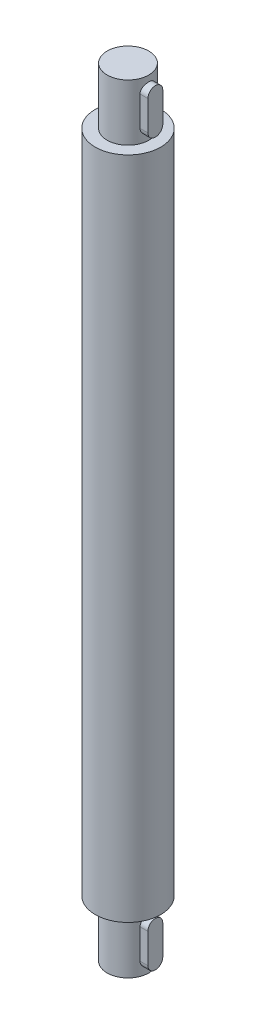
SolidWorks part; units mm, degrees
material "AISI 304"
ref_plane "Front Plane" through (0, 0, 0) normal (0, 0, 1) x (1, 0, 0)
ref_plane "Top Plane" through (0, 0, 0) normal (0, 1, 0) x (1, 0, 0)
ref_plane "Right Plane" through (0, 0, 0) normal (1, 0, 0) x (0, 0, -1)
sketch "Sketch1" plane through (0, 0, 0) normal (0, 1, 0) x (1, 0, 0)
  circle A0 centre (0, 0) radius 7
  dimension "D1" = 14
extrude "Boss-Extrude1" add sketch "Sketch1" along normal blind 19
sketch "Sketch2" plane through (0, 19, 0) normal (0, 1, 0) x (1, 0, 0)
  circle A0 centre (0, 0) radius 11
  dimension "D1" = 22
extrude "Boss-Extrude2" add sketch "Sketch2" along normal blind 223.5
sketch "Sketch3" plane through (0, 242.5, 0) normal (0, 1, 0) x (1, 0, 0)
  circle A0 centre (0, 0) radius 7
  dimension "D1" = 14
extrude "Boss-Extrude3" add sketch "Sketch3" along normal blind 19
ref_plane "Plane1" through (0, 130.75, 0) normal (0, 1, 0) x (1, 0, 0)
ref_axis "Axis1" through (0, 19, 7.7) along (0, 0, -1)
ref_plane "Plane2" through (7, 0, 0) normal (1, 0, 0) x (0, 0, -1)
sketch "Sketch4" plane through (7, 0, 0) normal (1, 0, 0) x (0, 0, -1)
  line L0 (0, 4.5) -> (0, 14.5) construction
  line L1 (-2.5, 4.5) -> (-2.5, 14.5)
  line L2 (2.5, 4.5) -> (2.5, 14.5)
  arc A0 (-2.5, 4.5) -> (2.5, 4.5) centre (0, 4.5) ccw
  arc A1 (2.5, 14.5) -> (-2.5, 14.5) centre (0, 14.5) ccw
  point P3 (0, 9.5)
  dimension "D1" = 5
  dimension "D2" = 4.5
  dimension "D3" = 10
extrude "Boss-Extrude4" add sketch "Sketch4" along normal blind 2.2 and the other way blind 3
mirror "Mirror1" about plane through (0, 130.75, 0) normal (0, 1, 0) of "Boss-Extrude4"
